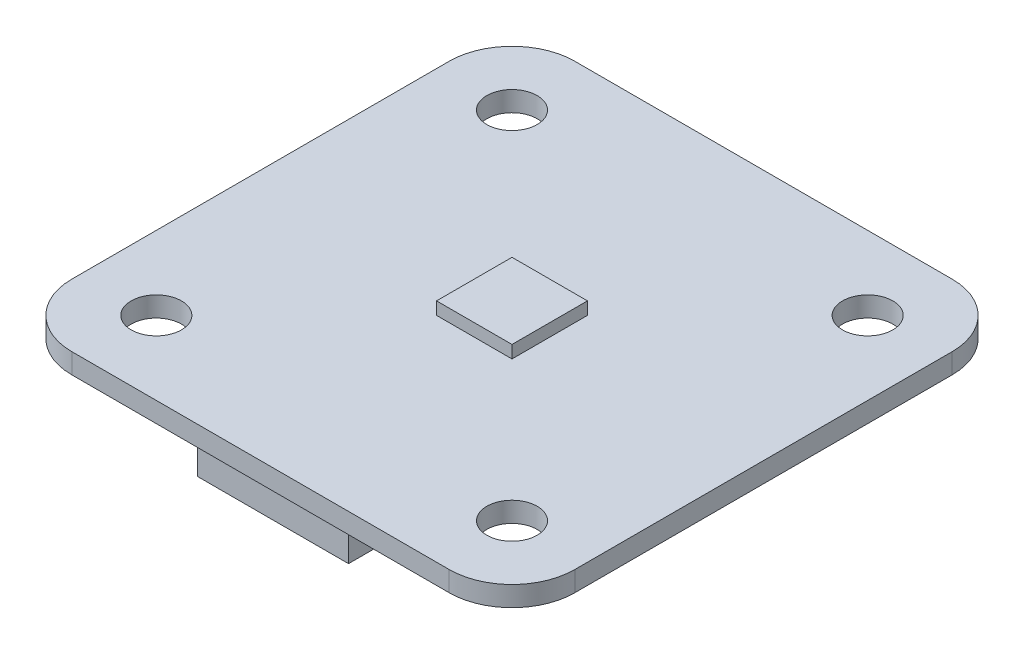
SolidWorks part; units mm, degrees
ref_plane "Front Plane" through (0, 0, 0) normal (0, 0, 1) x (1, 0, 0)
ref_plane "Top Plane" through (0, 0, 0) normal (0, 1, 0) x (1, 0, 0)
ref_plane "Right Plane" through (0, 0, 0) normal (1, 0, 0) x (0, 0, -1)
sketch "Sketch1" plane through (0, 0, 0) normal (0, 1, 0) x (1, 0, 0)
  line L1 (-20, 20) -> (20, 20)
  line L2 (-20, 20) -> (-20, -20)
  line L3 (-20, -20) -> (20, -20)
  line L4 (20, 20) -> (20, -20)
  line L5 (-20, 20) -> (20, -20) construction
  line L6 (-20, -20) -> (20, 20) construction
  point P0 (0, 0)
  dimension "D1" = 40
extrude "Boss-Extrude1" add sketch "Sketch1" along normal blind 1.6
fillet "Fillet1" radius 5 4 edges at (-20, 0.8, -20) (-20, 0.8, 20) (20, 0.8, -20) (20, 0.8, 20)
sketch "Sketch2" plane through (0, 1.6, 0) normal (0, 1, 0) x (1, 0, 0)
  line L0 (0, 0) -> (0, 20) construction
  line L1 (15, 20) -> (-15, 20) construction
  line L2 (0, 0) -> (-18.5355, 18.5355) construction
  arc A0 (-15, 20) -> (-20, 15) centre (-15, 15) ccw construction
  circle A1 centre (-14.1421, 14.1421) radius 2
  circle A2 centre (14.1421, 14.1421) radius 2
  circle A3 centre (-14.1421, -14.1421) radius 2
  circle A4 centre (14.1421, -14.1421) radius 2
  dimension "D2" = 4
  dimension "D3" = 20
  dimension "D1" = 45
  dimension "D4" = 20
extrude "Cut-Extrude1" cut sketch "Sketch2" against normal blind 1.6
sketch "Sketch3" plane through (0, 1.6, 0) normal (0, 1, 0) x (1, 0, 0)
  line L1 (-3, 3) -> (3, 3)
  line L2 (-3, 3) -> (-3, -3)
  line L3 (-3, -3) -> (3, -3)
  line L4 (3, 3) -> (3, -3)
  line L5 (-3, 3) -> (3, -3) construction
  line L6 (-3, -3) -> (3, 3) construction
  point P0 (0, 0)
  dimension "D1" = 6
extrude "Boss-Extrude2" add sketch "Sketch3" along normal blind 1
sketch "Sketch4" plane through (0, 0, 0) normal (0, -1, 0) x (1, 0, 0)
  line L0 (-15, 20) -> (15, 20) construction
  line L1 (-6, 19) -> (6, 19)
  line L2 (-6, 19) -> (-6, 11)
  line L3 (-6, 11) -> (6, 11)
  line L4 (6, 19) -> (6, 11)
  line L5 (-6, 19) -> (6, 11) construction
  line L6 (-6, 11) -> (6, 19) construction
  point P0 (0, 15)
  dimension "D1" = 12
  dimension "D2" = 8
  dimension "D3" = 1
extrude "Boss-Extrude3" add sketch "Sketch4" along normal blind 3
